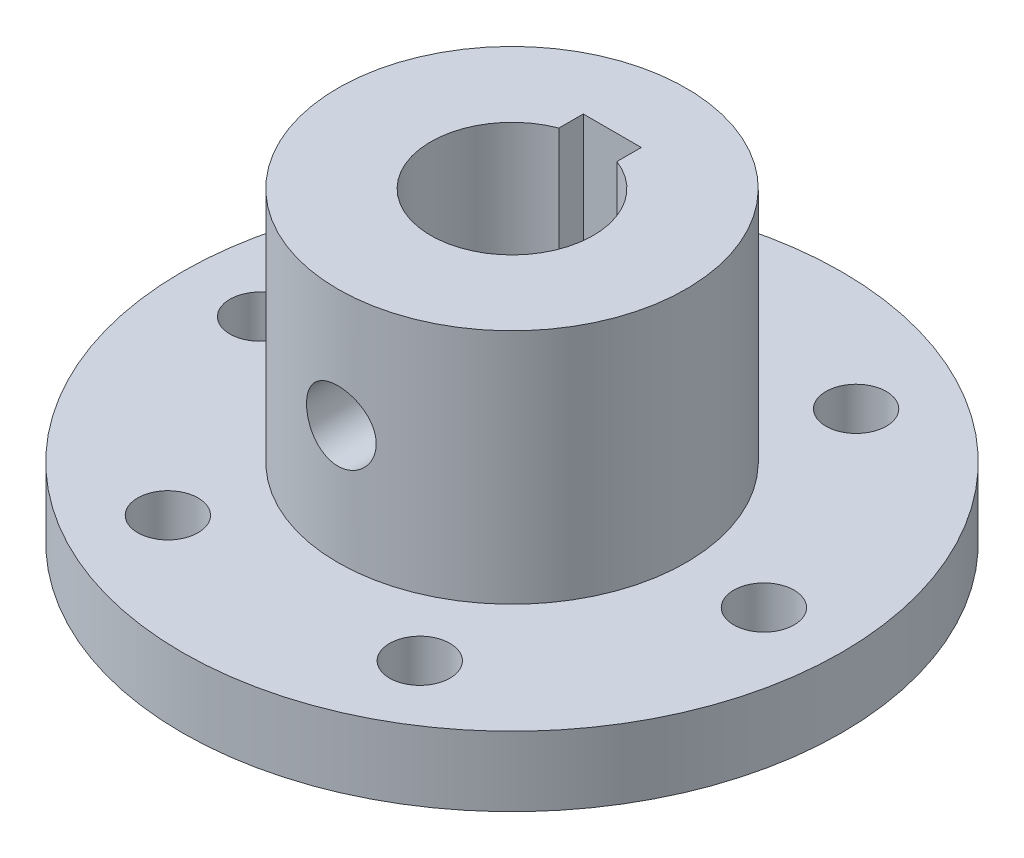
SolidWorks part; units mm, degrees
ref_plane "Front Plane" through (0, 0, 0) normal (0, 0, 1) x (1, 0, 0)
ref_plane "Top Plane" through (0, 0, 0) normal (0, 1, 0) x (1, 0, 0)
ref_plane "Right Plane" through (0, 0, 0) normal (1, 0, 0) x (0, 0, -1)
sketch "Sketch1" plane through (0, 0, 0) normal (0, 1, 0) x (1, 0, 0)
  circle A0 centre (0, 0) radius 28.4
  dimension "D1" = 56.8
extrude "Boss-Extrude1" add sketch "Sketch1" along normal blind 6
sketch "Sketch2" plane through (0, 6, 0) normal (0, 1, 0) x (1, 0, 0)
  circle A0 centre (0, 0) radius 15
  dimension "D1" = 30
extrude "Boss-Extrude2" add sketch "Sketch2" along normal blind 20.4
sketch "Sketch3" plane through (0, 26.4, 0) normal (0, 1, 0) x (1, 0, 0)
  line L1 (-2.5, 8.6383) -> (2.5, 8.6383)
  line L2 (-2.5, 8.6383) -> (-2.5, 6.5383)
  line L4 (2.5, 8.6383) -> (2.5, 6.5383)
  line L5 (-2.5, 8.6383) -> (2.5, 6.5383) construction
  line L6 (-2.5, 6.5383) -> (2.5, 8.6383) construction
  arc A0 (-2.5, 6.5383) -> (2.5, 6.5383) centre (0, 0) ccw
  point P7 (0, 7.5883)
  point P10 (0, 8.6383)
  dimension "D1" = 14
  dimension "D2" = 5
  dimension "D3" = 2.1
extrude "Cut-Extrude1" cut sketch "Sketch3" against normal through all
sketch "Sketch4" plane through (0, 0, 0) normal (0, 0, 1) x (1, 0, 0)
  line L0 (7, 26.4) -> (-7, 26.4) construction
  line L1 (0, 0) -> (0, 16.2) construction
  circle A0 centre (0, 16.2) radius 3
  dimension "D1" = 6
  dimension "D2" = 10.2
extrude "Cut-Extrude2" cut sketch "Sketch4" along normal through all
sketch "Sketch5" plane through (0, 6, 0) normal (0, 1, 0) x (1, 0, 0)
  line L0 (-21.7, 0) -> (-28.4, 0) construction
  line L1 (-21.7, 0) -> (-15, 0) construction
  line L2 (-21.7, 0) -> (-21.7, 18.3213) construction
  line L3 (-21.7, 0) -> (-21.7, -18.3213) construction
  circle A0 centre (-21.7, 0) radius 2.6
  circle A1 centre (0, 0) radius 28.4 construction
  circle A2 centre (0, 0) radius 15 construction
  dimension "D1" = 5.2
extrude "Cut-Extrude3" cut sketch "Sketch5" against normal through all
pattern_circular "CirPattern1" count 6 over 360 about axis through (0, 6, 0) along (0, 1, 0) of "Cut-Extrude3"
